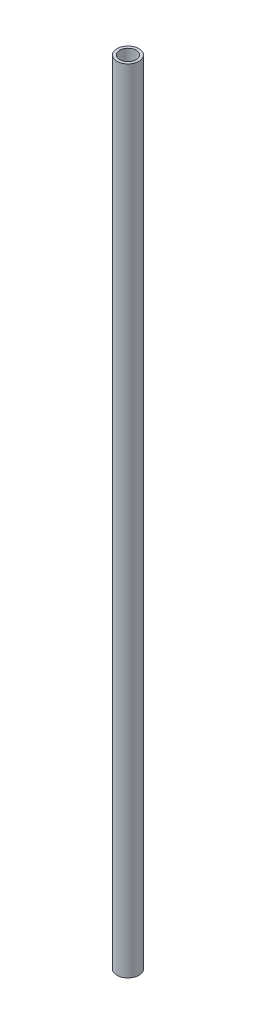
SolidWorks part; units mm, degrees
ref_plane "Front Plane" through (0, 0, 0) normal (0, 0, 1) x (1, 0, 0)
ref_plane "Top Plane" through (0, 0, 0) normal (0, 1, 0) x (1, 0, 0)
ref_plane "Right Plane" through (0, 0, 0) normal (1, 0, 0) x (0, 0, -1)
sketch "Sketch1" plane through (0, 0, 0) normal (0, 1, 0) x (1, 0, 0)
  circle A0 centre (0, 0) radius 12.7
  circle A1 centre (0, 0) radius 9.525
  dimension "D1" = 25.4
  dimension "D2" = 3.175
extrude "Boss-Extrude1" add sketch "Sketch1" along normal blind 914.4
equation "\"Pstrut_L\"= 36in"
equation "\"Pstrut_D\"= 1in"
equation "\"Pstrut_T\"= 0.25"
equation "\"Sstrut_L\"= 36in"
equation "\"Sstrut_D\"= 0.5in"
equation "\"Sstrut_T\"= 0.125"
equation "\"Dstrut_L\"= 10in"
equation "\"Dstrut_D\"= 0.5in"
equation "\"Dstrut_T\"= 0.125"
equation "\"D1@Sketch1\"=\"Pstrut_D\""
equation "\"D2@Sketch1\"=\"Dstrut_T\""
equation "\"D1@Boss-Extrude1\"=\"Pstrut_L\""
